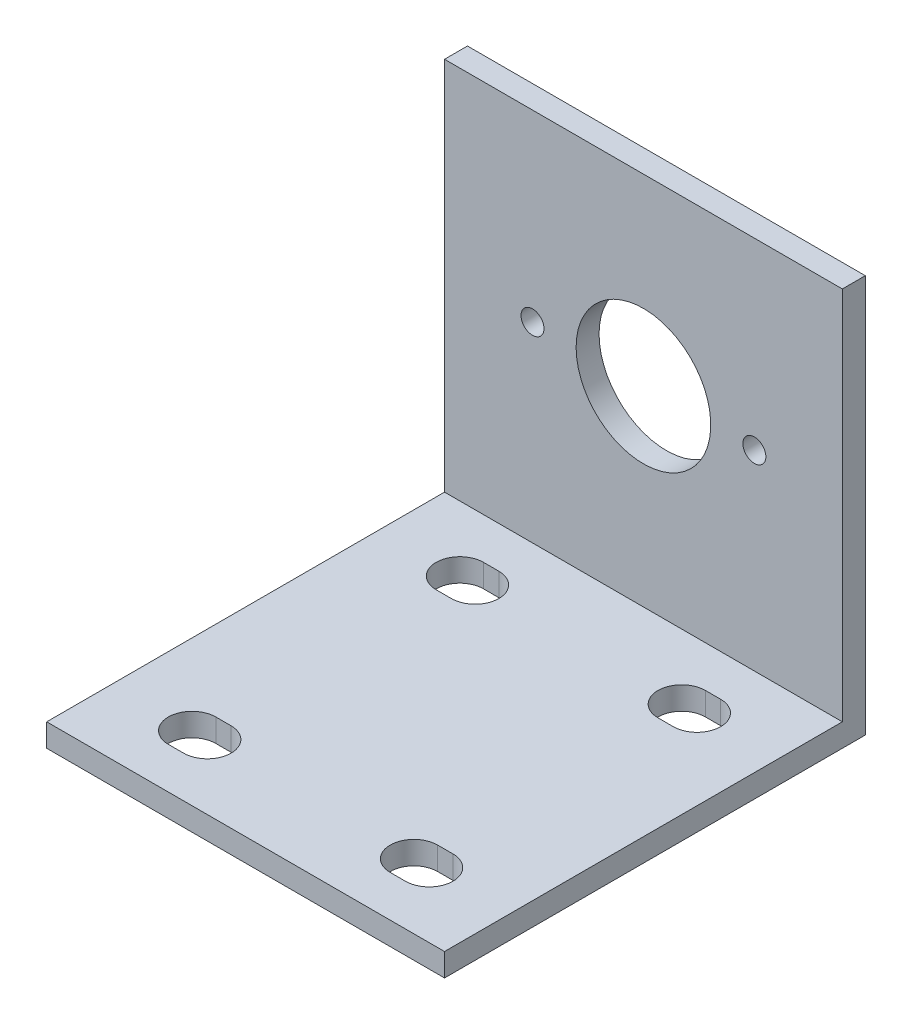
SolidWorks part; units mm, degrees
ref_plane "前基準面" through (0, 0, 0) normal (0, 0, 1) x (1, 0, 0)
ref_plane "上基準面" through (0, 0, 0) normal (0, 1, 0) x (1, 0, 0)
ref_plane "右基準面" through (0, 0, 0) normal (1, 0, 0) x (0, 0, -1)
sketch "草圖1" plane through (0, 0, 0) normal (0, 1, 0) x (1, 0, 0)
  line L0 (-15.5, 17.5) -> (-13.5, 17.5) construction
  line L1 (26, 26) -> (-26, 26)
  line L2 (26, 26) -> (26, -26)
  line L3 (26, -26) -> (-26, -26)
  line L4 (-26, 26) -> (-26, -26)
  line L5 (0, -26) -> (0, 26) construction
  line L6 (26, 0) -> (-26, 0) construction
  line L7 (-15.5, 20.6) -> (-13.5, 20.6)
  line L8 (-15.5, 14.4) -> (-13.5, 14.4)
  line L9 (15.5, 17.5) -> (13.5, 17.5) construction
  line L10 (15.5, 20.6) -> (13.5, 20.6)
  line L11 (15.5, 14.4) -> (13.5, 14.4)
  line L12 (15.5, -17.5) -> (13.5, -17.5) construction
  line L13 (15.5, -20.6) -> (13.5, -20.6)
  line L14 (15.5, -14.4) -> (13.5, -14.4)
  line L15 (-15.5, -17.5) -> (-13.5, -17.5) construction
  line L16 (-15.5, -20.6) -> (-13.5, -20.6)
  line L17 (-15.5, -14.4) -> (-13.5, -14.4)
  arc A0 (-15.5, 20.6) -> (-15.5, 14.4) centre (-15.5, 17.5) ccw
  arc A1 (-13.5, 14.4) -> (-13.5, 20.6) centre (-13.5, 17.5) ccw
  arc A2 (15.5, 20.6) -> (15.5, 14.4) centre (15.5, 17.5) cw
  arc A3 (13.5, 14.4) -> (13.5, 20.6) centre (13.5, 17.5) cw
  arc A4 (15.5, -20.6) -> (15.5, -14.4) centre (15.5, -17.5) ccw
  arc A5 (13.5, -14.4) -> (13.5, -20.6) centre (13.5, -17.5) ccw
  arc A6 (-15.5, -20.6) -> (-15.5, -14.4) centre (-15.5, -17.5) cw
  arc A7 (-13.5, -14.4) -> (-13.5, -20.6) centre (-13.5, -17.5) cw
  point P0 (0, 0)
  point P6 (-14.5, 17.5)
  point P14 (0, 0)
  point P15 (-11.3152, 14.0631)
  point P16 (-12.0733, 13.0522)
  point P19 (14.5, 17.5)
  point P26 (14.5, -17.5)
  point P33 (-14.5, -17.5)
  point P38 (13.7047, -12.5574)
  dimension "D3" = 3.1
  dimension "D1" = 52
  dimension "D2" = 52
  dimension "D4" = 2
  dimension "D5" = 35
  dimension "D6" = 29
extrude "填料-伸長1" add sketch "草圖1" along normal blind 3
sketch "草圖2" plane through (0, 0, -26) normal (0, 0, -1) x (-1, 0, 0)
  line L0 (-26, 3) -> (-26, 0) construction
  line L1 (26, 0) -> (-26, 0)
  line L2 (26, 0) -> (26, 52)
  line L3 (26, 52) -> (-26, 52)
  line L4 (-26, 0) -> (-26, 52)
  line L5 (0, 58.3104) -> (0, -5.5003) construction
  circle A0 centre (-14.5, 28) radius 1.5
  circle A1 centre (14.5, 28) radius 1.5
  circle A2 centre (0, 28) radius 8.8
  point P14 (0, 0)
  dimension "D2" = 3
  dimension "D5" = 17.6
  dimension "D1" = 52
  dimension "D3" = 29
  dimension "D4" = 24
extrude "填料-伸長2" add sketch "草圖2" along normal blind 3
